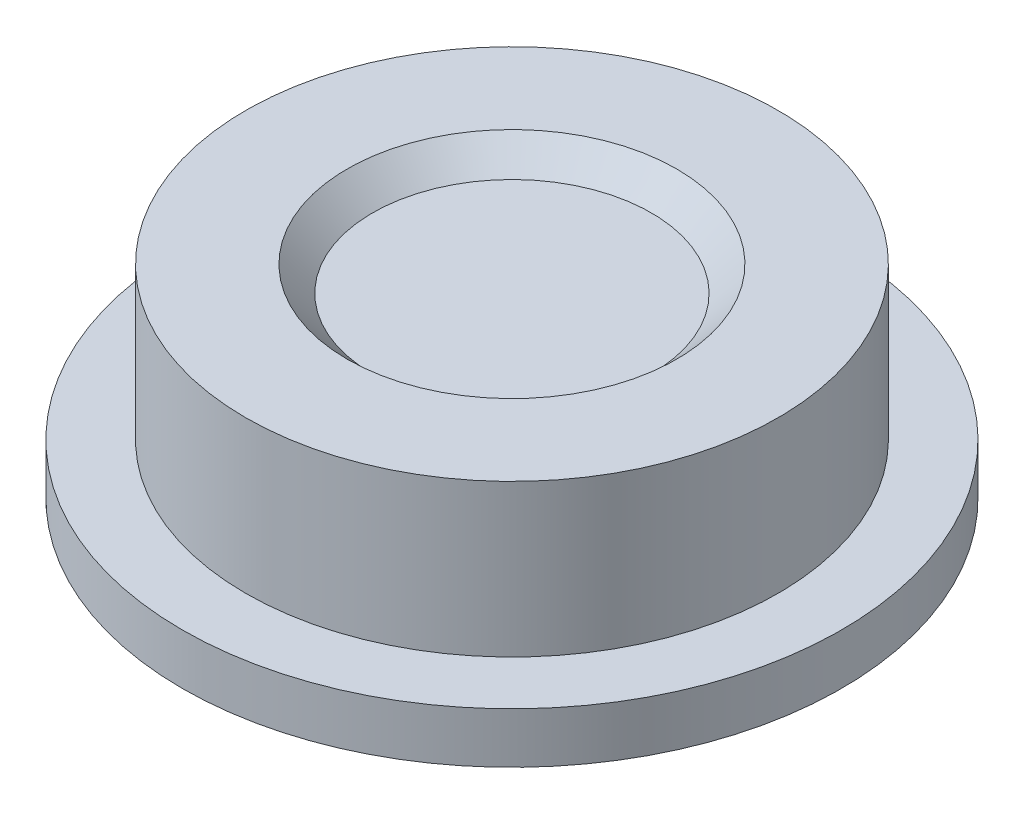
SolidWorks part; units mm, degrees
material "6061-T6 (SS)"
ref_plane "Front Plane" through (0, 0, 0) normal (0, 0, 1) x (1, 0, 0)
ref_plane "Top Plane" through (0, 0, 0) normal (0, 1, 0) x (1, 0, 0)
ref_plane "Right Plane" through (0, 0, 0) normal (1, 0, 0) x (0, 0, -1)
sketch "BaseS" plane through (0, 0, 0) normal (0, 1, 0) x (1, 0, 0)
  circle A0 centre (0, 0) radius 6.5
  dimension "Dia" = 13
extrude "Base" add sketch "BaseS" against normal blind 1
sketch "O-RingCaptureS" plane through (0, 0, 0) normal (0, 1, 0) x (1, 0, 0)
  circle A0 centre (0, 0) radius 5.25
  circle A1 centre (0, 0) radius 6.5 construction
  dimension "RefDia" = 10.5
  dimension "DiaControl" = 1.25
extrude "O-RingCapture" add sketch "O-RingCaptureS" along normal blind 3
sketch "TopBoreS" plane through (0, 3, 0) normal (0, 1, 0) x (1, 0, 0)
  circle A0 centre (0, 0) radius 3.25
  dimension "Dia" = 6.5
extrude "TopBore" cut sketch "TopBoreS" against normal blind 0.5
sketch "CylinderBoreS" plane through (0, -1, 0) normal (0, -1, 0) x (-1, 0, 0)
  circle A0 centre (0, 0) radius 1.5
  point P3 (0, 0)
  point P4 (0, 0)
  dimension "D1" = 3
chamfer "Chamfer1" distance 0.5 angle 45 1 edges at (0, 2.5, 3.25)
extrude "Cut-Extrude1" cut sketch "CylinderBoreS" against normal blind 1.5 draft 40
